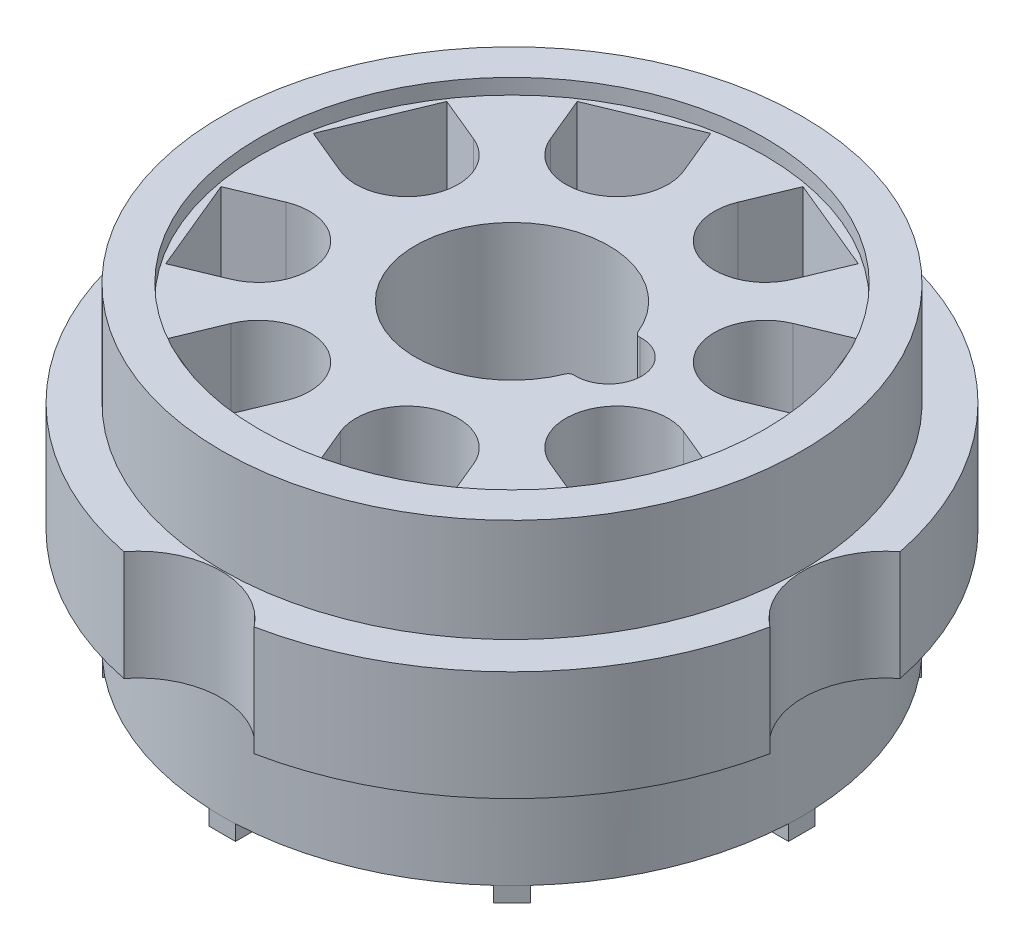
SolidWorks part; units mm, degrees
material "Ceramic Porcelain"
ref_plane "Front Plane" through (0, 0, 0) normal (0, 0, 1) x (1, 0, 0)
ref_plane "Top Plane" through (0, 0, 0) normal (0, 1, 0) x (1, 0, 0)
ref_plane "Right Plane" through (0, 0, 0) normal (1, 0, 0) x (0, 0, -1)
ref_axis "Axis1" through (0, 55, 0) along (0, -1, 0)
sketch "Sketch1" plane through (0, 0, 0) normal (0, 0, 1) x (1, 0, 0)
  line L0 (-13.2, 0) -> (-13.2, 4.7)
  line L1 (55, 0) -> (-55, 0) construction
  line L2 (-13.2, 4.7) -> (0, 4.7)
  line L3 (0, -55) -> (0, 55) construction
  line L4 (0, 4.7) -> (0, -9.7)
  line L5 (0, -9.7) -> (-13.2, -9.7)
  line L6 (-13.2, -9.7) -> (-13.2, -5)
  line L7 (-13.2, -5) -> (-15, -5)
  line L8 (-15, -5) -> (-15, 0)
  line L9 (-15, 0) -> (-13.2, 0)
  line L10 (0, 20.6449) -> (0, -32.7342) construction
  dimension "D1" = 26.4
  dimension "D2" = 30
  dimension "D3" = 4.7
  dimension "D4" = 5
  dimension "D5" = 9.7
revolve "Revolve1" add sketch "Sketch1" angle 360 about L10
sketch "Sketch2" plane through (0, 4.7, 0) normal (0, 1, 0) x (1, 0, 0)
  circle A0 centre (0, 0) radius 11.5
  dimension "D1" = 23
extrude "Extrude1" cut sketch "Sketch2" against normal blind 0.7
sketch "Sketch4" plane through (0, -9.7, 0) normal (0, -1, 0) x (1, 0, 0)
  circle A0 centre (0, 0) radius 6.5
  dimension "D1" = 13
extrude "Extrude3" add sketch "Sketch4" along normal blind 1
sketch "Sketch5" plane through (0, -9.7, 0) normal (0, -1, 0) x (1, 0, 0)
  line L0 (8.47, 0) -> (-8.47, 0) construction
  line L1 (6.4722, 0.6) -> (13.1864, 0.6)
  line L2 (6.4722, 0.6) -> (6.4722, -0.6)
  line L3 (6.4722, -0.6) -> (13.1864, -0.6)
  line L4 (13.1864, 0.6) -> (13.1864, -0.6)
  circle A0 centre (0, 0) radius 13.2 construction
  circle A1 centre (0, 0) radius 6.5 construction
  dimension "D1" = 0.6
  dimension "D2" = 1.2
extrude "Extrude4" add sketch "Sketch5" along normal blind 0.7
sketch "Sketch3" plane through (0, 0, 0) normal (0, 1, 0) x (1, 0, 0)
  arc A0 (4.0774, 1.6537) -> (4.0774, -1.6537) centre (0, 0) ccw
  arc A1 (4.3221, -1.498) -> (4.3221, 1.498) centre (4.4, 0) ccw
  arc A2 (4.0774, 1.6537) -> (4.3221, 1.498) centre (4.3091, 1.7476) ccw
  arc A3 (4.3221, -1.498) -> (4.0774, -1.6537) centre (4.3091, -1.7476) ccw
  dimension "D2" = 8.8
  dimension "D3" = 0.25
  dimension "D1" = 3
extrude "Extrude2" cut sketch "Sketch3" against normal through all and the other way through all
pattern_circular "CirPattern1" count 8 over 360 about axis through (0, 55, 0) along (0, -1, 0) of "Extrude4"
ref_plane "Plane1" through (0, 0, 0) normal (0.3827, 0, 0.9239) x (0.9239, 0, -0.3827)
sketch "Sketch7" plane through (0, 4, 0) normal (0, 1, 0) x (1, 0, 0)
  line L0 (9.3653, 6.3958) -> (11.1448, 2.0998)
  line L1 (9.0496, 1.2319) -> (11.1448, 2.0998)
  line L2 (9.3653, 6.3958) -> (7.2701, 5.5279)
  line L3 (-7.8253, -3.2413) -> (7.8253, 3.2413) construction
  arc A0 (7.2701, 5.5279) -> (9.0496, 1.2319) centre (8.1599, 3.3799) ccw
  dimension "D1" = 4.65
  dimension "D2" = 11.1
extrude "Extrude5" cut sketch "Sketch7" against normal blind 12.3
sketch "Sketch9" plane through (0, -9.7, 0) normal (0, -1, 0) x (1, 0, 0)
  line L0 (10.5618, -1.9394) -> (8.8397, -6.0969)
  line L1 (8.8397, -6.0969) -> (7.9158, -5.7142)
  line L2 (7.9158, -5.7142) -> (9.6379, -1.5568)
  line L3 (9.6379, -1.5568) -> (10.5618, -1.9394)
  line L4 (7.8253, -3.2413) -> (-7.8253, 3.2413) construction
  dimension "D1" = 4.5
  dimension "D2" = 2.25
  dimension "D3" = 1
  dimension "D4" = 10.5
extrude "Extrude6" cut sketch "Sketch9" against normal through all
pattern_circular "CirPattern2" count 8 over 360 about axis through (0, 55, 0) along (0, -1, 0) of "Extrude5", "Extrude6"
sketch "Sketch10" plane through (0, 0, 0) normal (0, 1, 0) x (1, 0, 0)
  line L0 (-8.47, 0) -> (8.47, 0) construction
  circle A0 centre (17, 0) radius 3.75
  dimension "D1" = 7.5
  dimension "D2" = 17
extrude "Extrude7" cut sketch "Sketch10" against normal blind 12.3
pattern_circular "CirPattern3" count 4 over 360 about axis through (0, 55, 0) along (0, -1, 0) of "Extrude7"
